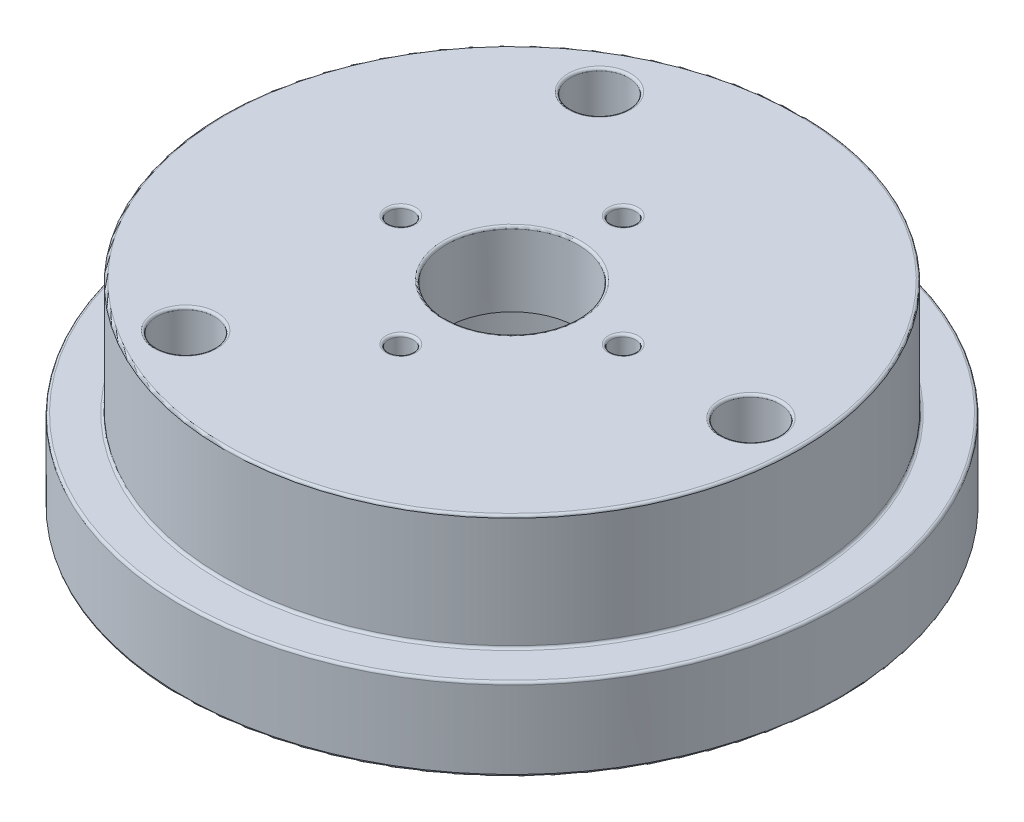
SolidWorks part; units mm, degrees
ref_plane "前视基准面" through (0, 0, 0) normal (0, 0, 1) x (1, 0, 0)
ref_plane "上视基准面" through (0, 0, 0) normal (0, 1, 0) x (1, 0, 0)
ref_plane "右视基准面" through (0, 0, 0) normal (1, 0, 0) x (0, 0, -1)
sketch "草图1" plane through (0, 0, 0) normal (0, 0, 1) x (1, 0, 0)
  line L0 (0, 0) -> (-20, 0)
  line L1 (-20, 0) -> (-20, 5)
  line L2 (-20, 5) -> (-17.5, 5)
  line L3 (-17.5, 5) -> (-17.5, 12)
  line L4 (-17.5, 12) -> (0, 12)
  line L5 (0, 12) -> (0, 0)
  dimension "D1" = 20
  dimension "D2" = 5
  dimension "D3" = 12
  dimension "D4" = 17.5
revolve "旋转1" add sketch "草图1" angle 360 about L5
sketch "草图2" plane through (0, 0, 0) normal (0, -1, 0) x (1, 0, 0)
  circle A0 centre (0, 0) radius 10
  circle A1 centre (14.5, 0) radius 1.75
  circle A2 centre (-7.25, -12.5574) radius 1.75
  circle A3 centre (-7.25, 12.5574) radius 1.75
  circle A4 centre (0, 0) radius 20 construction
  circle A5 centre (0, 0) radius 4
  circle A6 centre (6.75, 0) radius 0.75
  circle A7 centre (0, -6.75) radius 0.75
  circle A8 centre (-6.75, 0) radius 0.75
  circle A9 centre (0, 6.75) radius 0.75
  point P12 (0, 0)
  point P24 (0, 0)
  dimension "D1" = 20
  dimension "D2" = 3.5
  dimension "D7" = 8
  dimension "D8" = 1.5
  dimension "D3" = 14.5
  dimension "D5" = 14.5
  dimension "D6" = 7.25
  dimension "D9" = 6.75
  dimension "D11" = 6.75
  dimension "D4" = 3
  dimension "D10" = 4
extrude "切除-拉伸1" cut sketch "草图2" against normal through all contours A5 | A2 | A7 | A6 | A8 | A9 | A1 | A3 region at (14.5, 0, 0) region at (-7.25, 0, -12.5574) region at (-7.25, 0, 12.5574) region at (0, 0, 0) region at (6.75, 0, 0) region at (0, 0, -6.75) region at (-6.75, 0, 0) region at (0, 0, 6.75)
extrude "切除-拉伸2" cut sketch "草图2<3>" against normal blind 7.5
sketch "草图2<3>" plane through (0, 0, 0) normal (0, -1, 0) x (1, 0, 0) same geometry as "草图2"
fillet "圆角1" radius 0.15 16 edges at (-20, 0, 0) (-5.5, 0, 12.5574) (16.25, 0, 0) (-5.5, 0, -12.5574) (10, 0, 0) (-17.5, 5, 0) (-20, 5, 0) (-17.5, 12, 0) (4, 12, 0) (-5.5, 12, 12.5574) (16.25, 12, 0) (0.75, 12, 6.75) (-6, 12, 0) (7.5, 12, 0) (0.75, 12, -6.75) (-5.5, 12, -12.5574)
